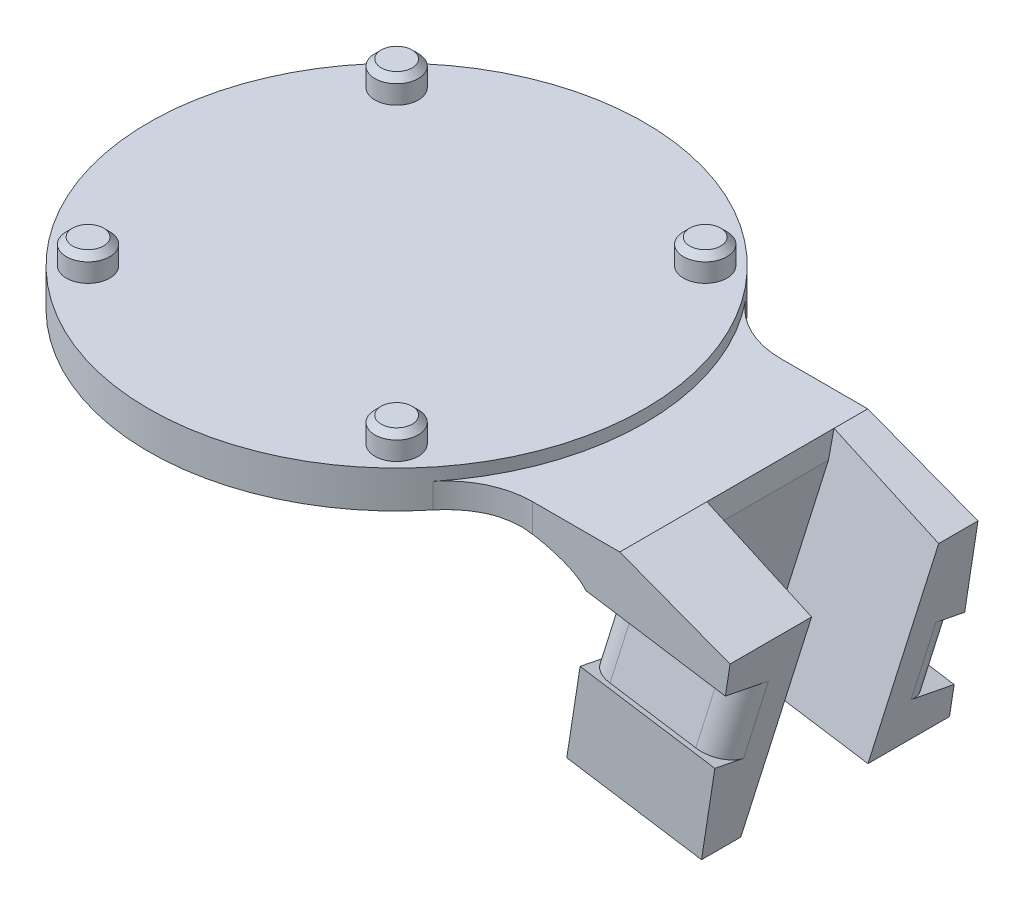
SolidWorks part; units mm, degrees
ref_plane "Front Plane" through (0, 0, 0) normal (0, 0, 1) x (1, 0, 0)
ref_plane "Top Plane" through (0, 0, 0) normal (0, 1, 0) x (1, 0, 0)
ref_plane "Right Plane" through (0, 0, 0) normal (1, 0, 0) x (0, 0, -1)
sketch "Sketch1" plane through (0, 0, 0) normal (0, 1, 0) x (1, 0, 0)
  circle A0 centre (0, 0) radius 20
extrude "Boss-Extrude1" add sketch "Sketch1" along normal blind 1
sketch "Sketch2" plane through (0, 0, 0) normal (0, -1, 0) x (1, 0, 0)
  line L0 (0, 0) -> (28, 0)
  line L1 (0, 0) -> (0, 10)
  line L2 (0, 0) -> (0, -10)
  line L3 (0, -10) -> (28, -10)
  line L4 (28, -10) -> (28, 0)
  line L5 (28, 10) -> (0, 10)
  line L6 (28, 0) -> (28, 10)
  circle A0 centre (0, 0) radius 20
  circle M2 centre (0, 0) radius 20
extrude "Boss-Extrude2" add sketch "Sketch2" along normal blind 2 contours L5 L3 L2 L1 M2 | L5 L1 L0 M2 | L2 L3 L0 M2 | L3 L4 L0 M2 | L0 L6 L5 M2
sketch "Sketch3" plane through (0, 0, 10) normal (0, 0, 1) x (1, 0, 0)
  line L0 (28, -2) -> (25.7, -16.8226)
  line L1 (25.7, -16.8226) -> (23.7237, -16.516)
  line L2 (23.7237, -16.516) -> (25.9761, -2)
  line L3 (28, -2) -> (17.3205, -2) construction
  line L4 (25.9761, -2) -> (28, -2)
extrude "Boss-Extrude3" add sketch "Sketch3" against normal up to surface (20 mm away) up to face at (22.6603, -1, -10)
sketch "Sketch4" plane through (27.6447, -4.2895, 0) normal (0.9882, -0.1533, 0) x (0, 0, -1)
  line L0 (0, -5.1831) -> (4.8757, -6.2908) construction
  line L1 (0, -5.1831) -> (0, 2.3169) construction
  line L2 (10, 2.3169) -> (-10, 2.3169) construction
  line L3 (0, -5.1831) -> (10, -5.1831) construction
  line L5 (10, 2.3169) -> (10, -12.6831) construction
  line L6 (0, -5.1831) -> (-4.8757, -4.0753) construction
  line L7 (-4.8757, -4.0753) -> (-6.8314, -12.6831)
  line L8 (10, -12.6831) -> (-10, -12.6831) construction
  line L9 (-4.8757, -4.0753) -> (-3.4235, 2.3169)
  line L10 (4.8757, -6.2908) -> (3.4235, -12.6831)
  line L11 (4.8757, -6.2908) -> (6.8314, 2.3169)
  line L12 (6.8314, 2.3169) -> (10, 2.3169)
  line L13 (10, 2.3169) -> (10, -12.6831)
  line L14 (10, -12.6831) -> (3.4235, -12.6831)
  line L15 (-3.4235, 2.3169) -> (-10, 2.3169)
  line L16 (-10, 2.3169) -> (-10, -12.6831)
  line L17 (-10, -12.6831) -> (-6.8314, -12.6831)
extrude "Boss-Extrude4" add sketch "Sketch4" along normal blind 9
sketch "Sketch5" plane through (36.5383, -5.6695, 0) normal (0.9882, -0.1533, 0) x (0, 0, -1)
  line L0 (-3.4235, 2.3169) -> (3.4235, -12.6831) construction
  line L1 (-6.8314, -12.6831) -> (6.8314, 2.3169) construction
  line L2 (10, 2.3169) -> (6.8314, 2.3169) construction
  line L3 (0, -5.1831) -> (-10, -2.9111) construction
  line L4 (-10, 2.3169) -> (-10, -12.6831) construction
  line L5 (0, -5.1831) -> (10, -7.455) construction
  line L6 (10, -12.6831) -> (10, 2.3169) construction
  line L7 (-11.6497, -5.3033) -> (-9.5459, -5.7813)
  line L8 (-11.6497, -5.3033) -> (-10.4541, -0.041)
  line L9 (-9.5459, -5.7813) -> (-8.3503, -0.519)
  line L10 (-10.4541, -0.041) -> (-8.3503, -0.519)
  line L11 (-11.6497, -5.3033) -> (-8.3503, -0.519) construction
  line L12 (-9.5459, -5.7813) -> (-10.4541, -0.041) construction
  line L13 (0, -5.1831) -> (0.5162, -2.9111) construction
  line L14 (8.3503, -9.8472) -> (9.5459, -4.5849)
  line L15 (11.6497, -5.0628) -> (9.5459, -4.5849)
  line L16 (10.4541, -10.3252) -> (11.6497, -5.0628)
  line L17 (10.4541, -10.3252) -> (8.3503, -9.8472)
extrude "Cut-Extrude1" cut sketch "Sketch5" against normal blind 15
fillet "Fillet4" radius 1.65 1 edges at (25.9761, -2, 0)
chamfer "Chamfer3" distance 2 distance2 9 2 edges at (28, -2, -8.4157) (28, -2, 6.7117)
fillet "Fillet5" radius 2 4 edges at (35.4319, -12.8002, -8.9481) (36.0553, -8.7824, 8.9481) (24.562, -11.1136, -8.9481)
sketch "Sketch9" plane through (0, 1, 0) normal (0, 1, 0) x (1, 0, 0)
  line L0 (0, 0) -> (12.4451, 12.4451) construction
  line L1 (0, 0) -> (-12.4451, -12.4451) construction
  line L2 (0, 0) -> (12.4451, -12.4451) construction
  line L3 (12.4451, -12.4451) -> (-12.4451, 12.4451) construction
  circle A0 centre (0, 0) radius 17.6
  circle A1 centre (12.4451, -12.4451) radius 1.75
  circle A2 centre (-12.4451, -12.4451) radius 1.75
  circle A3 centre (-12.4451, 12.4451) radius 1.75
  circle A4 centre (12.4451, 12.4451) radius 1.75
extrude "Boss-Extrude5" add sketch "Sketch9" along normal blind 2 contours A0 A4 | A0 A4 | A0 A1 | A0 A1 | A0 A2 | A0 A2 | A0 A3 | A0 A3
chamfer "Chamfer4" distance 0.5 angle 45 4 edges at (-12.4451, 3, 14.1951) (12.4451, 3, 14.1951) (-12.4451, 3, -10.6951) (12.4451, 3, -10.6951)
fillet "Fillet6" radius 7 2 edges at (17.3205, -1, -10) (17.3205, -1, 10)
